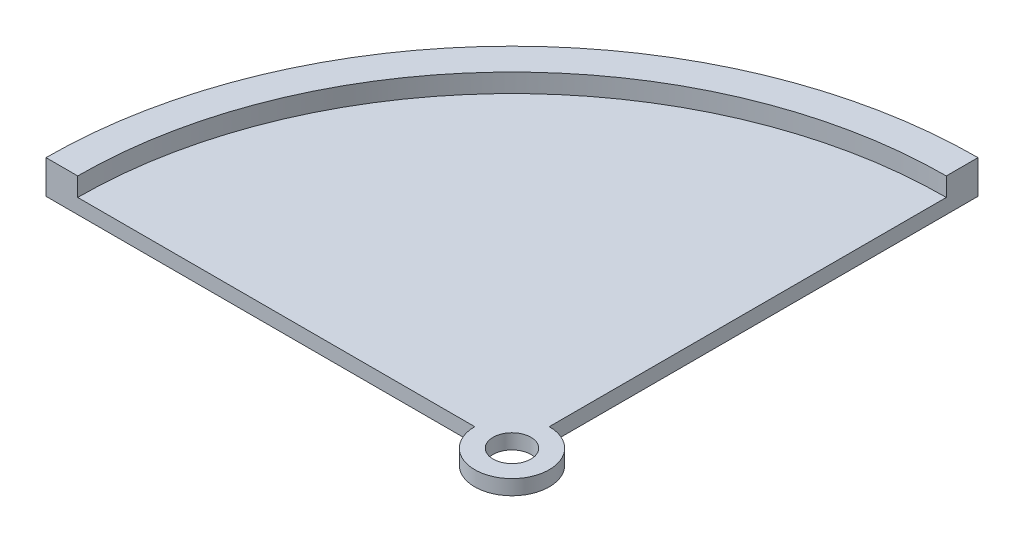
SolidWorks part; units mm, degrees
ref_plane "Front Plane" through (0, 0, 0) normal (0, 0, 1) x (1, 0, 0)
ref_plane "Top Plane" through (0, 0, 0) normal (0, 1, 0) x (1, 0, 0)
ref_plane "Right Plane" through (0, 0, 0) normal (1, 0, 0) x (0, 0, -1)
sketch "Sketch1" plane through (0, 0, 0) normal (0, 1, 0) x (1, 0, 0)
  line L1 (-62.5, 62.5) -> (62.5, 62.5)
  line L2 (-62.5, 62.5) -> (-62.5, -62.5)
  line L3 (-62.5, -62.5) -> (62.5, -62.5)
  line L4 (62.5, 62.5) -> (62.5, -62.5)
  line L5 (-62.5, 62.5) -> (62.5, -62.5) construction
  line L6 (-62.5, -62.5) -> (62.5, 62.5) construction
  circle A0 centre (62.5, -62.5) radius 55.5 construction
  point P0 (0, 0)
  point P7 (0, 0)
  dimension "D2" = 111
  dimension "D3" = 125
  dimension "D1" = 125
extrude "Boss-Extrude1" add sketch "Sketch1" along normal blind 4
sketch "Sketch2" plane through (0, 4, 0) normal (0, 1, 0) x (1, 0, 0)
  line L0 (-62.5, -62.5) -> (-62.5, 62.5)
  line L1 (-62.5, 62.5) -> (62.5, 62.5)
  line L2 (62.5, 62.5) -> (62.5, 54)
  line L3 (62.5, -62.5) -> (62.5, 62.5) construction
  line L4 (-62.5, -62.5) -> (-54, -62.5)
  line L5 (-62.5, -62.5) -> (62.5, -62.5) construction
  arc A0 (-54, -62.5) -> (62.5, 54) centre (62.5, -62.5) cw
  circle A1 centre (62.5, -62.5) radius 55.5 construction
  point P17 (-24.902, -55.5)
  dimension "D1" = 111
  dimension "D2" = 61
extrude "Boss-Extrude2" add sketch "Sketch2" along normal blind 5
sketch "Sketch3" plane through (0, 4, 0) normal (0, 1, 0) x (1, 0, 0)
  circle A0 centre (62.5, -62.5) radius 10
  dimension "D1" = 20
extrude "Boss-Extrude3" add sketch "Sketch3" against normal up to surface (4 mm away) up to face at (0, 0, 0)
sketch "Sketch4" plane through (0, 4, 0) normal (0, 1, 0) x (1, 0, 0)
  circle A0 centre (62.5, -62.5) radius 5.075
  dimension "D1" = 10.15
extrude "Cut-Extrude1" cut sketch "Sketch4" against normal up to surface (4 mm away) up to face at (12.9142, 0, 12.9142)
fillet "Fillet1" radius 125 1 edges at (-62.5, 4.5, -62.5)
